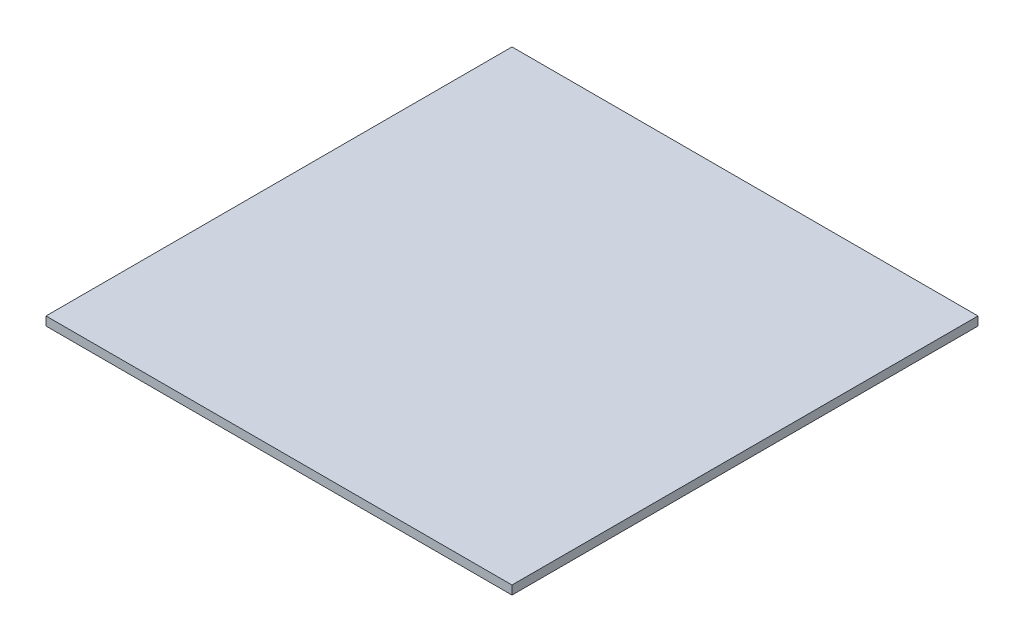
SolidWorks part; units mm, degrees
material "Cedar"
ref_plane "Front" through (0, 0, 0) normal (0, 0, 1) x (1, 0, 0)
ref_plane "Top" through (0, 0, 0) normal (0, 1, 0) x (1, 0, 0)
ref_plane "Right" through (0, 0, 0) normal (1, 0, 0) x (0, 0, -1)
sketch "Sketch1" plane through (0, 0, 0) normal (0, 1, 0) x (1, 0, 0)
  line L1 (-304.8, -304.8) -> (304.8, -304.8)
  line L2 (-304.8, -304.8) -> (-304.8, 304.8)
  line L3 (-304.8, 304.8) -> (304.8, 304.8)
  line L4 (304.8, -304.8) -> (304.8, 304.8)
  line L5 (-304.8, -304.8) -> (304.8, 304.8) construction
  line L6 (-304.8, 304.8) -> (304.8, -304.8) construction
  point P0 (0, 0)
  dimension "D1" = 609.6
  dimension "D2" = 609.6
extrude "Boss-Extrude1" add sketch "Sketch1" along normal blind 11.4554
